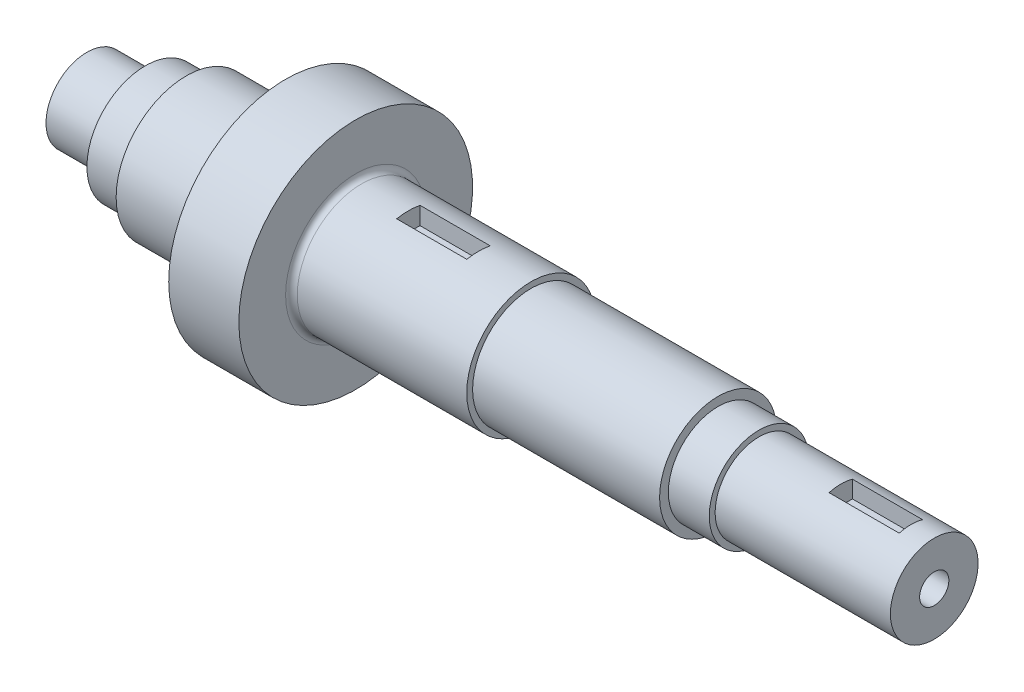
SolidWorks part; units mm, degrees
ref_plane "Front Plane" through (0, 0, 0) normal (0, 0, 1) x (1, 0, 0)
ref_plane "Top Plane" through (0, 0, 0) normal (0, 1, 0) x (1, 0, 0)
ref_plane "Right Plane" through (0, 0, 0) normal (1, 0, 0) x (0, 0, -1)
other "Center of Mass"
sketch "Sketch3" plane through (0, 0, 0) normal (0, 0, 1) x (1, 0, 0)
  line L0 (0, 0) -> (0, 39.0464) construction
  line L1 (-72.5, 0) -> (72.5, 0) construction
  line L2 (-72.5, 2.5) -> (-72.5, 0) construction
  line L3 (-72.5, 2.5) -> (-72.5, 7)
  line L4 (-72.5, 7) -> (-62.5, 7)
  line L5 (-62.5, 7) -> (-62.5, 10)
  line L6 (-62.5, 10) -> (-55.5, 10)
  line L7 (-55.5, 10) -> (-55.5, 12)
  line L8 (-55.5, 12) -> (-38.5, 12)
  line L9 (-38.5, 12) -> (-38.5, 20)
  line L10 (-38.5, 20) -> (-26.5, 20)
  line L11 (-26.5, 20) -> (-26.5, 11)
  line L12 (-26.5, 11) -> (3.5, 11)
  line L13 (3.5, 11) -> (3.5, 10)
  line L14 (3.5, 10) -> (35.5, 10)
  line L15 (35.5, 10) -> (35.5, 8.5)
  line L17 (72.5, 7.5) -> (72.5, 2.5)
  line L18 (72.5, 2.5) -> (-72.5, 2.5)
  line L19 (-32.5, 20) -> (-32.5, 2.5) construction
  line L20 (-11.5, 11) -> (-11.5, 2.5) construction
  line L21 (-77.5, 12) -> (-72.8417, 12) construction
  line L22 (-62.5, 10) -> (-62.5, 16) construction
  line L23 (-77.5, 15) -> (-72.8417, 15) construction
  line L24 (35.5, 8.5) -> (42.5, 8.5)
  line L25 (11.9511, 11) -> (20.8732, 11) construction
  line L26 (30.861, 12) -> (33.3773, 12) construction
  line L27 (42.5, 8.5) -> (42.5, 7.5)
  line L36 (42.5, 7.5) -> (72.5, 7.5)
  line L38 (35.5, 8.5) -> (44.5, 8.5) construction
  point P5 (0, 0)
  point P39 (0, 0)
  point P42 (0, 0)
  point P43 (0, 0)
  dimension "D3" = 40
  dimension "D2" = 22
  dimension "D4" = 40
  dimension "D5" = 12
  dimension "D6" = 10
  dimension "D7" = 7
  dimension "D9" = 5
  dimension "D10" = 14
  dimension "D11" = 20
  dimension "D12" = 12
  dimension "D13" = 24
  dimension "D14" = 32
  dimension "D15" = 15
  dimension "D16" = 20
  dimension "D18" = 11
  dimension "D20" = 12
  dimension "D21" = 7
  dimension "D22" = 17
  dimension "D24" = 15
  dimension "D8" = 30
  dimension "D17" = 32
  dimension "D19" = 30
revolve "Revolve1" add sketch "Sketch3" angle 360 about L1
ref_plane "Plane1" through (0, 11, 0) normal (0, 1, 0) x (1, 0, 0)
sketch "Sketch4" plane through (0, 11, 0) normal (0, 1, 0) x (1, 0, 0)
  line L0 (3.5, 0) -> (-26.5, 0) construction
  line L1 (3.5, -11) -> (3.5, 11) construction
  line L2 (-26.5, -11) -> (-26.5, 11) construction
  line L3 (-11.5, 0) -> (-11.5, 23.5234) construction
  line L4 (72.5, -7.5) -> (72.5, 7.5) construction
  line L5 (72.5, 0) -> (62.5, 0) construction
  line L6 (-17.5, -2) -> (-5.5, -2)
  line L7 (-17.5, -2) -> (-17.5, 2)
  line L8 (-17.5, 2) -> (-5.5, 2)
  line L9 (-5.5, -2) -> (-5.5, 2)
  line L10 (-17.5, -2) -> (-5.5, 2) construction
  line L11 (-17.5, 2) -> (-5.5, -2) construction
  line L16 (56.5, -2) -> (68.5, -2)
  line L17 (56.5, -2) -> (56.5, 2)
  line L18 (56.5, 2) -> (68.5, 2)
  line L19 (68.5, -2) -> (68.5, 2)
  line L20 (56.5, -2) -> (68.5, 2) construction
  line L21 (56.5, 2) -> (68.5, -2) construction
  point P17 (62.5, 0)
  dimension "D1" = 12
  dimension "D2" = 4
  dimension "D3" = 10
  dimension "D4" = 12
  dimension "D5" = 4
extrude "Cut-Extrude1" cut sketch "Sketch4" against normal blind 3.2 contours L6 L9 L8 L7
fillet "Fillet1" radius 1 2 edges at (-26.5, 0, 11) (-38.5, 0, 12)
ref_plane "Plane2" through (0, 7.5, 0) normal (0, 1, 0) x (1, 0, 0)
sketch "Sketch5" plane through (0, 7.5, 0) normal (0, 1, 0) x (1, 0, 0)
  line L0 (68.5, -2) -> (68.5, 2) construction
  line L1 (56.5, -2) -> (68.5, -2) construction
  line L2 (56.5, -2) -> (56.5, 2) construction
  line L3 (56.5, 2) -> (68.5, 2) construction
  line L4 (68.5, -2) -> (68.5, 2)
  line L5 (56.5, -2) -> (68.5, -2)
  line L6 (56.5, -2) -> (56.5, 2)
  line L7 (56.5, 2) -> (68.5, 2)
extrude "Cut-Extrude3" cut sketch "Sketch5" against normal blind 3.2 contours L5 L4 L7 L6
equation "\"mainShaft-D\"= 20mm"
equation "\"mainTrackGear-D\"= 40mm"
equation "\"D4@Sketch3\"=\"mainTrackGear-D\""
equation "\"D11@Sketch3\"=\"mainShaft-D\""
